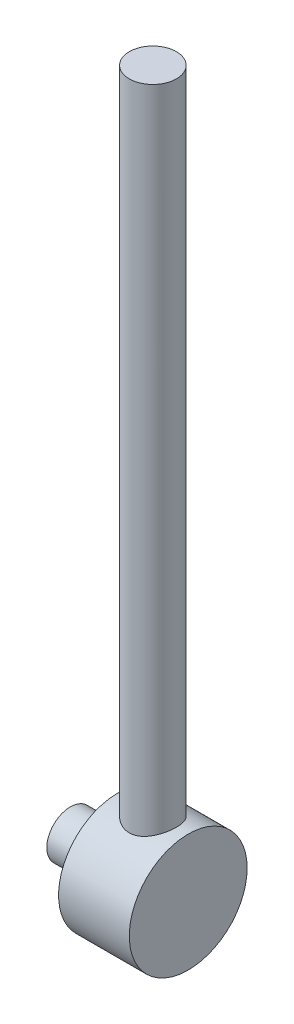
SolidWorks part; units mm, degrees
material "普通碳钢"
ref_plane "前视基准面" through (0, 0, 0) normal (0, 0, 1) x (1, 0, 0)
ref_plane "上视基准面" through (0, 0, 0) normal (0, 1, 0) x (1, 0, 0)
ref_plane "右视基准面" through (0, 0, 0) normal (1, 0, 0) x (0, 0, -1)
sketch "草图1" plane through (0, 0, 0) normal (1, 0, 0) x (0, 0, -1)
  circle A0 centre (0, 0) radius 5
  circle A1 centre (0, 0) radius 12.5
  dimension "D1" = 10
  dimension "D2" = 25
extrude "凸台-拉伸1" add sketch "草图1" along normal blind 15 contours A0 | A1 A0 region at (0, 0, 0) region at (0, 0, 12.1464)
extrude "凸台-拉伸2" add sketch "草图1<3>" against normal blind 10 contours A0 region at (0, 0, 0)
sketch "草图1<3>" plane through (0, 0, 0) normal (1, 0, 0) x (0, 0, -1) same geometry as "草图1"
ref_plane "基准面1" through (0, 150, 0) normal (0, 1, 0) x (1, 0, 0)
sketch "草图2" plane through (0, 150, 0) normal (0, 1, 0) x (1, 0, 0)
  line L0 (7.5, 12.5) -> (7.5, -12.5) construction
  line L1 (15, 12.5) -> (0, 12.5) construction
  line L2 (0, -12.5) -> (15, -12.5) construction
  circle A0 centre (7.5, 0) radius 5
  dimension "D1" = 10
extrude "凸台-拉伸3" add sketch "草图2" against normal up to surface (138.5436 mm away) up to face at (15, 0, -12.5)
